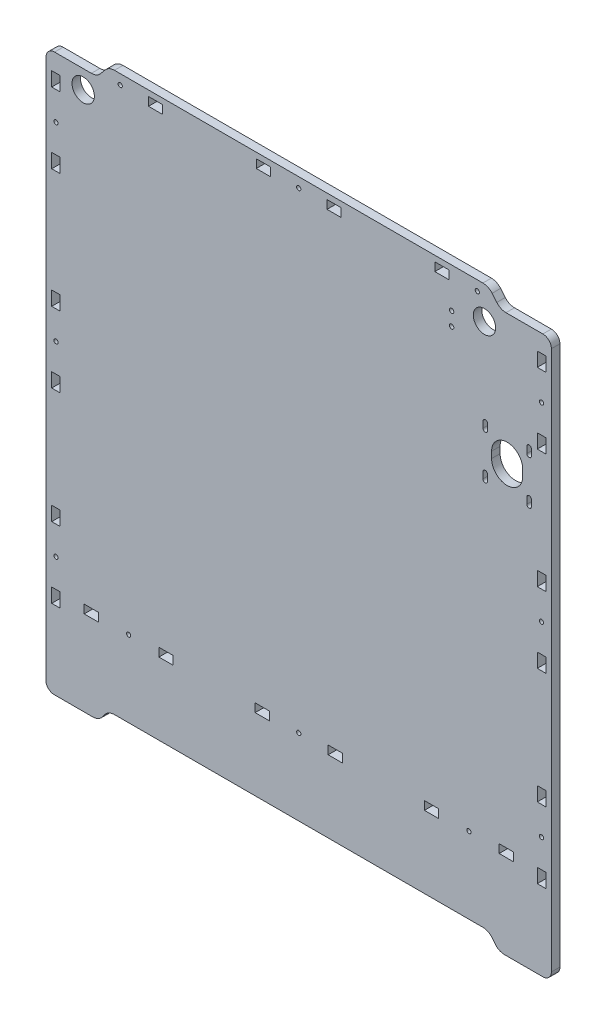
SolidWorks part; units mm, degrees
ref_plane "Спереди" through (0, 0, 0) normal (0, 0, 1) x (1, 0, 0)
ref_plane "Сверху" through (0, 0, 0) normal (0, 1, 0) x (1, 0, 0)
ref_plane "Справа" through (0, 0, 0) normal (1, 0, 0) x (0, 0, -1)
sketch "Эскиз1" plane through (0, 0, 0) normal (0, 0, 1) x (1, 0, 0)
  line L0 (133.6555, 83.4698) -> (133.6555, 87.9698)
  line L1 (133.6555, 118.9698) -> (133.6555, 114.4698)
  line L2 (130.4555, 83.4698) -> (130.4555, 87.9698)
  line L3 (158.5555, 98.9698) -> (158.5555, 103.4698)
  line L4 (130.4555, 118.9698) -> (130.4555, 114.4698)
  line L5 (161.4555, 118.9698) -> (161.4555, 114.4698)
  line L6 (164.6555, 118.9698) -> (164.6555, 114.4698)
  line L7 (136.5555, 98.9698) -> (136.5555, 103.4698)
  line L8 (161.4555, 83.4698) -> (161.4555, 87.9698)
  line L9 (164.6555, 83.4698) -> (164.6555, 87.9698)
  line L10 (-174.1809, 36.7423) -> (-174.1809, 46.7423)
  line L11 (99.1091, -139.9977) -> (89.1091, -139.9977)
  line L12 (89.1091, -139.9977) -> (89.1091, -133.9977)
  line L13 (89.1091, -133.9977) -> (99.1091, -133.9977)
  line L14 (99.1091, -133.9977) -> (99.1091, -139.9977)
  line L15 (151.9091, -139.9977) -> (141.9091, -139.9977)
  line L16 (141.9091, -139.9977) -> (141.9091, -133.9977)
  line L17 (141.9091, -133.9977) -> (151.9091, -133.9977)
  line L18 (151.9091, -133.9977) -> (151.9091, -139.9977)
  line L19 (-19.6709, 193.3023) -> (-29.6709, 193.3023)
  line L20 (-29.6709, 193.3023) -> (-29.6709, 199.3023)
  line L21 (-29.6709, 199.3023) -> (-19.6709, 199.3023)
  line L22 (-19.6709, 199.3023) -> (-19.6709, 193.3023)
  line L23 (30.3091, 193.3023) -> (20.3091, 193.3023)
  line L24 (20.3091, 193.3023) -> (20.3091, 199.3023)
  line L25 (20.3091, 199.3023) -> (30.3091, 199.3023)
  line L26 (30.3091, 199.3023) -> (30.3091, 193.3023)
  line L27 (-141.2709, -139.9977) -> (-151.2709, -139.9977)
  line L28 (-151.2709, -139.9977) -> (-151.2709, -133.9977)
  line L29 (-151.2709, -133.9977) -> (-141.2709, -133.9977)
  line L30 (-141.2709, -133.9977) -> (-141.2709, -139.9977)
  line L31 (-88.4709, -139.9977) -> (-98.4709, -139.9977)
  line L32 (-98.4709, -139.9977) -> (-98.4709, -133.9977)
  line L33 (-98.4709, -133.9977) -> (-88.4709, -133.9977)
  line L34 (-88.4709, -133.9977) -> (-88.4709, -139.9977)
  line L35 (-20.4709, -139.9977) -> (-30.4709, -139.9977)
  line L36 (-30.4709, -139.9977) -> (-30.4709, -133.9977)
  line L37 (-30.4709, -133.9977) -> (-20.4709, -133.9977)
  line L38 (-20.4709, -133.9977) -> (-20.4709, -139.9977)
  line L39 (31.1091, -139.9977) -> (21.1091, -139.9977)
  line L40 (21.1091, -139.9977) -> (21.1091, -133.9977)
  line L41 (21.1091, -133.9977) -> (31.1091, -133.9977)
  line L42 (31.1091, -133.9977) -> (31.1091, -139.9977)
  line L43 (-174.1809, 46.7423) -> (-168.1809, 46.7423)
  line L44 (-168.1809, 46.7423) -> (-168.1809, 36.7423)
  line L45 (-168.1809, 36.7423) -> (-174.1809, 36.7423)
  line L46 (-174.1809, -13.2577) -> (-174.1809, -3.2577)
  line L47 (-174.1809, -3.2577) -> (-168.1809, -3.2577)
  line L48 (-168.1809, -3.2577) -> (-168.1809, -13.2577)
  line L49 (-168.1809, -13.2577) -> (-174.1809, -13.2577)
  line L50 (-174.1809, 170.9023) -> (-174.1809, 180.9023)
  line L51 (-174.1809, 180.9023) -> (-168.1809, 180.9023)
  line L52 (-168.1809, 180.9023) -> (-168.1809, 170.9023)
  line L53 (-168.1809, 170.9023) -> (-174.1809, 170.9023)
  line L54 (-174.1809, 120.9023) -> (-174.1809, 130.9023)
  line L55 (-174.1809, 130.9023) -> (-168.1809, 130.9023)
  line L56 (-168.1809, 130.9023) -> (-168.1809, 120.9023)
  line L57 (-168.1809, 120.9023) -> (-174.1809, 120.9023)
  line L58 (-174.1809, -94.9877) -> (-174.1809, -84.9877)
  line L59 (-174.1809, -84.9877) -> (-168.1809, -84.9877)
  line L62 (-174.1809, -144.9777) -> (-174.1809, -134.9777)
  line L63 (-174.1809, -134.9777) -> (-168.1809, -134.9777)
  line L64 (-168.1809, -134.9777) -> (-168.1809, -144.9777)
  line L65 (-168.1809, -144.9777) -> (-174.1809, -144.9777)
  line L66 (168.8191, 36.7421) -> (168.8191, 46.7421)
  line L67 (168.8191, 46.7421) -> (174.8191, 46.7421)
  line L68 (174.8191, 46.7421) -> (174.8191, 36.7421)
  line L69 (174.8191, 36.7421) -> (168.8191, 36.7421)
  line L70 (168.8191, -13.2579) -> (168.8191, -3.2579)
  line L71 (168.8191, -3.2579) -> (174.8191, -3.2579)
  line L72 (174.8191, -3.2579) -> (174.8191, -13.2579)
  line L73 (174.8191, -13.2579) -> (168.8191, -13.2579)
  line L74 (168.8191, -94.9879) -> (168.8191, -84.9879)
  line L75 (168.8191, -84.9879) -> (174.8191, -84.9879)
  line L76 (174.8191, -84.9879) -> (174.8191, -94.9879)
  line L77 (174.8191, -94.9879) -> (168.8191, -94.9879)
  line L78 (168.8191, -144.9779) -> (168.8191, -134.9779)
  line L79 (168.8191, -134.9779) -> (174.8191, -134.9779)
  line L80 (174.8191, -134.9779) -> (174.8191, -144.9779)
  line L81 (174.8191, -144.9779) -> (168.8191, -144.9779)
  line L82 (168.8191, 170.9021) -> (168.8191, 180.9021)
  line L83 (168.8191, 180.9021) -> (174.8191, 180.9021)
  line L84 (175.1452, 170.9021) -> (168.8191, 170.9021)
  line L85 (168.8191, 120.9021) -> (168.8191, 130.9021)
  line L86 (168.8191, 130.9021) -> (174.8191, 130.9021)
  line L87 (174.8191, 130.9021) -> (174.8191, 120.9021)
  line L88 (174.8191, 120.9021) -> (168.8191, 120.9021)
  line L89 (-105.8209, 199.3023) -> (-95.8209, 199.3023)
  line L90 (-95.8209, 199.3023) -> (-95.8209, 193.3023)
  line L91 (-95.8209, 193.3023) -> (-105.8209, 193.3023)
  line L92 (-105.8209, 193.3023) -> (-105.8209, 199.3023)
  line L94 (96.4591, 193.3023) -> (96.4591, 199.3023)
  line L96 (146.7284, 193.3021) -> (172.7648, 193.3021)
  line L97 (106.4591, 193.3023) -> (96.4591, 193.3023)
  line L99 (-136.3916, 200.266) -> (-139.6874, 196.3386)
  line L100 (130.4099, 203.3023) -> (-129.8802, 203.3023)
  line L101 (136.9212, 200.266) -> (140.2171, 196.3385)
  line L102 (174.8191, 170.9781) -> (175.1452, 170.9021)
  line L104 (96.4591, 199.3023) -> (106.4591, 199.3023)
  line L105 (174.8191, 180.9021) -> (174.8191, 170.9781)
  line L106 (139.2171, -196.9614) -> (136.9212, -193.9418)
  line L107 (-129.8802, -190.9055) -> (130.4099, -190.9055)
  line L108 (-172.2352, -199.9977) -> (-145.1988, -199.9977)
  line L109 (-138.6874, -196.9614) -> (-136.3916, -193.9418)
  line L110 (172.7648, -199.9977) -> (145.7284, -199.9977)
  line L111 (-178.1809, 187.3023) -> (-178.1809, -195.6332)
  line L112 (178.8191, 187.3133) -> (178.8191, -193.9977)
  line L113 (-174.1809, -94.9877) -> (-168.1809, -94.9877)
  line L114 (-168.1809, -94.9877) -> (-168.1809, -84.9877)
  line L115 (-172.1809, 193.3023) -> (-146.1988, 193.3023)
  line L116 (106.4591, 199.3023) -> (106.4591, 193.3023)
  line L117 (-198.706, -139.9977) -> (230.9068, -139.9977) construction
  arc A0 (158.5555, 103.4698) -> (136.5555, 103.4698) centre (147.5555, 103.4698) ccw
  arc A1 (161.4555, 83.4698) -> (164.6555, 83.4698) centre (163.0555, 83.4698) ccw
  arc A2 (136.5555, 98.9698) -> (158.5555, 98.9698) centre (147.5555, 98.9698) ccw
  arc A3 (130.4555, 83.4698) -> (133.6555, 83.4698) centre (132.0555, 83.4698) ccw
  arc A4 (164.6555, 87.9698) -> (161.4555, 87.9698) centre (163.0555, 87.9698) ccw
  circle A5 centre (108.3191, 165.6023) radius 1.55
  circle A6 centre (108.3191, 175.3023) radius 1.55
  arc A7 (130.4555, 114.4698) -> (133.6555, 114.4698) centre (132.0555, 114.4698) ccw
  arc A8 (133.6555, 118.9698) -> (130.4555, 118.9698) centre (132.0555, 118.9698) ccw
  arc A9 (164.6555, 118.9698) -> (161.4555, 118.9698) centre (163.0555, 118.9698) ccw
  arc A10 (161.4555, 114.4698) -> (164.6555, 114.4698) centre (163.0555, 114.4698) ccw
  arc A11 (133.6555, 87.9698) -> (130.4555, 87.9698) centre (132.0555, 87.9698) ccw
  circle A12 centre (131.5191, 180.3023) radius 7.9
  circle A13 centre (-151.9809, 180.3023) radius 7.9
  arc A14 (-129.8802, 203.3023) -> (-136.3916, 200.266) centre (-129.8802, 194.8023) ccw
  arc A15 (-146.1988, 193.3023) -> (-139.6874, 196.3386) centre (-146.1988, 201.8023) ccw
  arc A17 (140.2171, 196.3385) -> (146.7284, 193.3021) centre (146.7286, 201.8021) ccw
  arc A18 (136.9212, 200.266) -> (130.4099, 203.3023) centre (130.4099, 194.8023) ccw
  arc A19 (178.8191, 187.3133) -> (172.7648, 193.3021) centre (172.8191, 187.3023) ccw
  arc A20 (136.9212, -193.9418) -> (130.4099, -190.9055) centre (130.4099, -199.4055) ccw
  arc A21 (-178.1809, -195.6332) -> (-172.2352, -199.9977) centre (-172.4074, -194.0002) ccw
  arc A22 (-145.1988, -199.9977) -> (-138.6874, -196.9614) centre (-145.1988, -191.4977) ccw
  arc A23 (139.2171, -196.9614) -> (145.7284, -199.9977) centre (145.7284, -191.4977) ccw
  arc A24 (-129.8802, -190.9055) -> (-136.3916, -193.9418) centre (-129.8802, -199.4055) ccw
  circle A25 centre (-171.1809, 150.9023) radius 1.5
  arc A26 (172.7648, -199.9977) -> (178.8191, -193.9977) centre (172.8191, -193.998) ccw
  circle A27 centre (-171.1809, 16.7423) radius 1.5
  circle A28 centre (171.8191, 150.9021) radius 1.5
  circle A29 centre (126.4591, 196.3023) radius 1.5
  circle A30 centre (-125.8209, 196.3023) radius 1.5
  circle A31 centre (0.3191, 196.3023) radius 1.5
  circle A32 centre (-119.8709, -136.9977) radius 1.5
  circle A33 centre (-171.1809, -114.9677) radius 1.5
  circle A34 centre (0.3191, -136.9977) radius 1.5
  circle A35 centre (120.5091, -136.9977) radius 1.5
  circle A36 centre (171.8191, -114.9679) radius 1.5
  circle A37 centre (171.8191, 16.7421) radius 1.5
  arc A38 (-178.1809, 187.3023) -> (-172.1809, 193.3023) centre (-172.1809, 187.3023) cw
  point P149 (159.2466, -199.9977)
  point P190 (-105.8209, 196.3023)
  point P191 (171.8191, -13.2579)
  point P192 (174.8191, -89.9879)
  point P193 (-100.8209, 193.3023)
  point P194 (20.3091, 196.3023)
  dimension "D9" = 15.8
  dimension "D24" = 8.5
  dimension "D25" = 8.5
  dimension "D26" = 6
  dimension "D27" = 8.5
  dimension "D28" = 8.5
  dimension "D29" = 4
  dimension "D30" = 6
  dimension "D32" = 12.4
  dimension "D40" = 20
  dimension "D82" = 9.7
  dimension "D83" = 28
  dimension "D84" = 70.5
  dimension "D112" = 3
  dimension "D3" = 10
  dimension "D4" = 20
  dimension "D5" = 20
  dimension "D6" = 10
  dimension "D7" = 6
  dimension "D8" = 6
  dimension "D10" = 74.16
  dimension "D11" = 10
  dimension "D12" = 6
  dimension "D13" = 20
  dimension "D14" = 6
  dimension "D15" = 10
  dimension "D16" = 71.73
  dimension "D17" = 6
  dimension "D18" = 10
  dimension "D19" = 20.01
  dimension "D20" = 10
  dimension "D21" = 20
  dimension "D22" = 403.3
  dimension "D23" = 19.98
  dimension "D31" = 10
  dimension "D33" = 10
  dimension "D34" = 55.02
  dimension "D35" = 6
  dimension "D36" = 10.0002
  dimension "D37" = 12.4
  dimension "D38" = 10
  dimension "D39" = 20
  dimension "D41" = 6
  dimension "D42" = 6
  dimension "D43" = 74.16
  dimension "D44" = 10
  dimension "D45" = 6
  dimension "D46" = 20
  dimension "D47" = 20
  dimension "D48" = 6
  dimension "D49" = 10
  dimension "D50" = 71.73
  dimension "D51" = 6
  dimension "D52" = 10
  dimension "D53" = 19.98
  dimension "D54" = 10
  dimension "D55" = 6
  dimension "D56" = 20.01
  dimension "D57" = 403.3
  dimension "D58" = 283.5
  dimension "D59" = 55.0198
  dimension "D60" = 357
  dimension "D61" = 26.2
  dimension "D62" = 47.3
  dimension "D63" = 23
  dimension "D64" = 23
  dimension "D65" = 7
  dimension "D66" = 4
  dimension "D67" = 4
  dimension "D68" = 7
  dimension "D69" = 4
  dimension "D70" = 4
  dimension "D71" = 7
  dimension "D72" = 4
  dimension "D73" = 4
  dimension "D74" = 7
  dimension "D75" = 4
  dimension "D76" = 4
  dimension "D77" = 7
  dimension "D78" = 4
  dimension "D79" = 4
  dimension "D80" = 7
  dimension "D81" = 4
  dimension "D85" = 7
  dimension "D86" = 4
  dimension "D87" = 10
  dimension "D88" = 6
  dimension "D89" = 6
  dimension "D90" = 10
  dimension "D91" = 4
  dimension "D92" = 7
  dimension "D93" = 10
  dimension "D94" = 6
  dimension "D95" = 4
  dimension "D96" = 7
  dimension "D97" = 4
  dimension "D98" = 6
  dimension "D99" = 52.36
  dimension "D100" = 20
  dimension "D101" = 66.15
  dimension "D102" = 52.36
  dimension "D103" = 20
  dimension "D104" = 10
  dimension "D105" = 66.15
  dimension "D106" = 178.5
  dimension "D107" = 19.99
  dimension "D108" = 19.99
  dimension "D109" = 60
  dimension "D110" = 10
  dimension "D111" = 6
  dimension "D113" = 10
  dimension "D114" = 6
  dimension "D115" = 10
  dimension "D116" = 6
  dimension "D117" = 3
  dimension "D118" = 6
  dimension "D119" = 10
  dimension "D120" = 10
  dimension "D121" = 6
  dimension "D122" = 3
  dimension "D123" = 6
  dimension "D124" = 10
  dimension "D125" = 178.5
  dimension "D126" = 16.91
  dimension "D127" = 21.4
  dimension "D128" = 21.4
  dimension "D129" = 58
  dimension "D130" = 16.91
  dimension "D131" = 21.4
  dimension "D132" = 21.4
  dimension "D133" = 58
extrude "Бобышка-Вытянуть1" add sketch "Эскиз1" along normal blind 6
